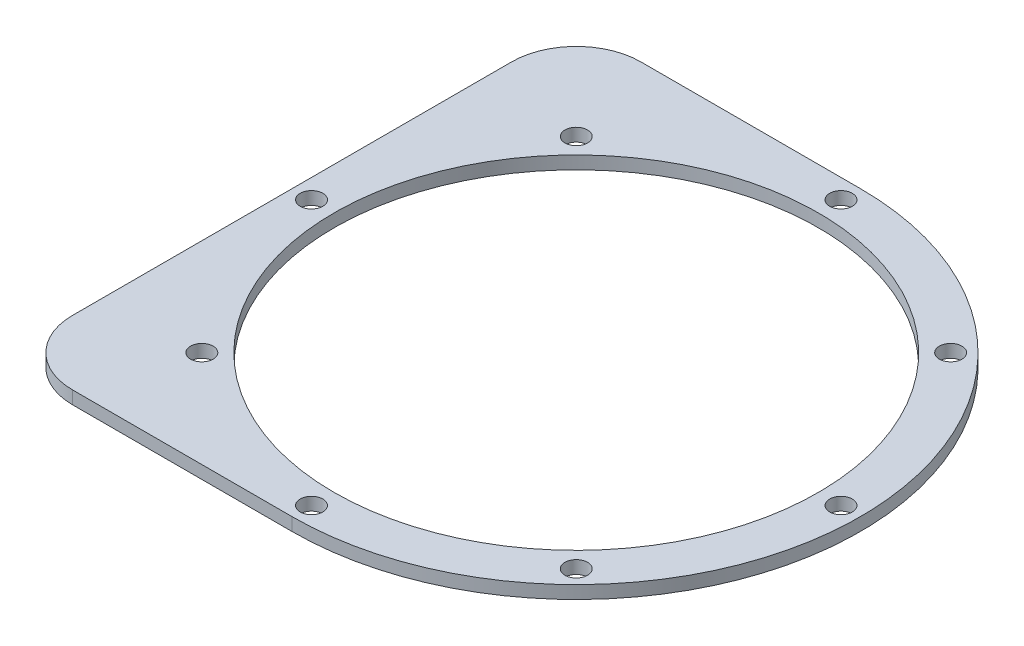
SolidWorks part; units mm, degrees
ref_plane "Front Plane" through (0, 0, 0) normal (0, 0, 1) x (1, 0, 0)
ref_plane "Top Plane" through (0, 0, 0) normal (0, 1, 0) x (1, 0, 0)
ref_plane "Right Plane" through (0, 0, 0) normal (1, 0, 0) x (0, 0, -1)
sketch "Sketch1" plane through (0, 0, 0) normal (0, 1, 0) x (1, 0, 0)
  circle A0 centre (0, 0) radius 44
  dimension "D1" = 88
extrude "Boss-Extrude1" add sketch "Sketch1" along normal blind 2
sketch "Sketch2" plane through (0, 2, 0) normal (0, 1, 0) x (1, 0, 0)
  line L1 (0, -44) -> (-44, -44)
  line L2 (0, -44) -> (0, 44)
  line L3 (0, 44) -> (-44, 44)
  line L4 (-44, -44) -> (-44, 44)
  line L5 (0, -44) -> (-44, 44) construction
  line L6 (0, 44) -> (-44, -44) construction
  circle A0 centre (0, 0) radius 44 construction
  point P0 (-22, 0)
extrude "Boss-Extrude2" add sketch "Sketch2" against normal up to surface (2 mm away) up to face at (0, 0, 44)
sketch "Sketch3" plane through (0, 2, 0) normal (0, 1, 0) x (1, 0, 0)
  circle A0 centre (41, 0) radius 1.75
  dimension "D1" = 3.5
  dimension "D2" = 41
extrude "Cut-Extrude1" cut sketch "Sketch3" against normal through all
pattern_circular "CirPattern1" count 8 over 360 about axis through (0, 2, 0) along (0, -1, 0) of "Cut-Extrude1" reverse direction yes
sketch "Sketch4" plane through (0, 2, 0) normal (0, 1, 0) x (1, 0, 0)
  circle A0 centre (0, 0) radius 37.5
  dimension "D1" = 75
extrude "Cut-Extrude2" cut sketch "Sketch4" against normal through all
fillet "Fillet1" radius 10 2 edges at (-44, 1, 44) (-44, 1, -44)
